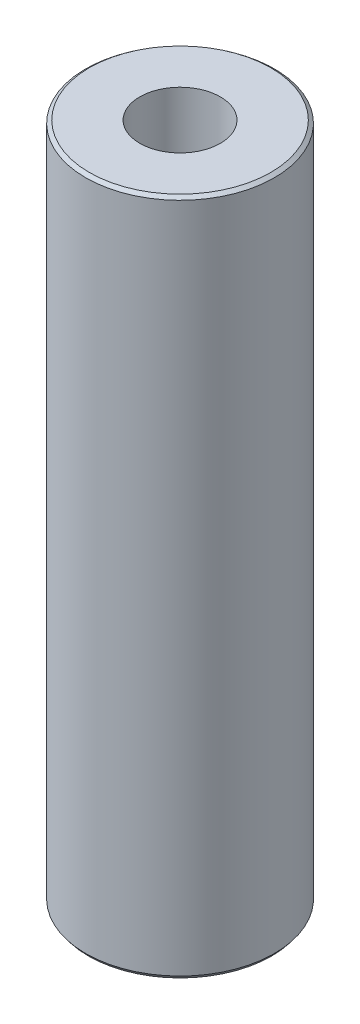
SolidWorks part; units mm, degrees
ref_plane "Front Plane" through (0, 0, 0) normal (0, 0, 1) x (1, 0, 0)
ref_plane "Top Plane" through (0, 0, 0) normal (0, 1, 0) x (1, 0, 0)
ref_plane "Right Plane" through (0, 0, 0) normal (1, 0, 0) x (0, 0, -1)
sketch "Sketch1" plane through (0, 0, 0) normal (0, 1, 0) x (1, 0, 0)
  circle A0 centre (0, 0) radius 25
  dimension "SHAFT_OD" = 50
extrude "Boss-Extrude1" add sketch "Sketch1" along normal blind 179.695
sketch "Sketch2" plane through (0, 0, 0) normal (0, 1, 0) x (1, 0, 0)
  circle A0 centre (0, 0) radius 10.6766
  dimension "BORE_D" = 21.3532
extrude "Cut-Extrude1" cut sketch "Sketch2" along normal through all
chamfer "Chamfer1" distance 0.7334 angle 52.596 2 edges at (0, 179.695, 25) (0, 0, 25) first distance on face at (0, 179.695, 25) first distance on face at (0, 0, 10.6766)
